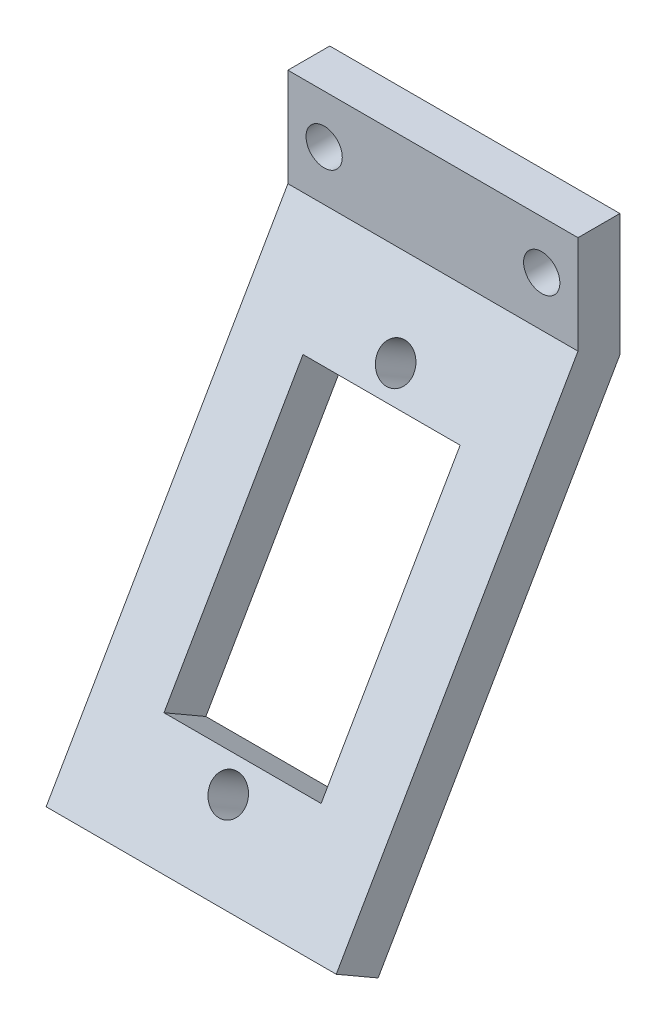
SolidWorks part; units mm, degrees
ref_plane "前视基准面" through (0, 0, 0) normal (0, 0, 1) x (1, 0, 0)
ref_plane "上视基准面" through (0, 0, 0) normal (0, 1, 0) x (1, 0, 0)
ref_plane "右视基准面" through (0, 0, 0) normal (1, 0, 0) x (0, 0, -1)
ref_axis "基准轴1" through (73.7735, 0, 0) along (-1, 0, 0)
ref_plane "基准面2" through (0, 0, 0) normal (0, 0.5, 0.866) x (-1, 0, 0)
ref_axis "基准轴2" through (0, 0, 97.5114) along (0, 0, -1)
ref_plane "基准面3" through (0, 43, 74.4782) normal (0, 0.5, 0.866) x (-1, 0, 0)
sketch "草图4" plane through (0, 43, 74.4782) normal (0, 0.5, 0.866) x (-1, 0, 0)
  line L1 (-6.5, -11.5) -> (6.5, -11.5)
  line L2 (-6.5, -11.5) -> (-6.5, 11.5)
  line L3 (-6.5, 11.5) -> (6.5, 11.5)
  line L4 (6.5, -11.5) -> (6.5, 11.5)
  line L5 (-6.5, -11.5) -> (6.5, 11.5) construction
  line L6 (-6.5, 11.5) -> (6.5, -11.5) construction
  line L7 (-12, -20) -> (12, -20)
  line L8 (-12, -20) -> (-12, 20)
  line L9 (-12, 20) -> (12, 20)
  line L10 (12, -20) -> (12, 20)
  line L11 (-12, -20) -> (12, 20) construction
  line L12 (-12, 20) -> (12, -20) construction
  point P0 (0, 0)
  point P6 (0, 0)
  dimension "D1" = 13
  dimension "D2" = 23
  dimension "D3" = 40
  dimension "D4" = 24
ref_axis "基准轴3" through (0, 77.466, 0) along (0, -1, 0)
ref_plane "基准面4" through (0, 75, 0) normal (0, 1, 0) x (1, 0, 0)
sketch "草图7" plane through (0, 43, 74.4782) normal (0, 0.5, 0.866) x (-1, 0, 0)
  line L0 (0, 48.7557) -> (0, -37.4519) construction
  line L1 (-73.7735, 0) -> (73.7735, 0) construction
  line L2 (0, 0) -> (14.5173, 0) construction
  circle A0 centre (0, 13.85) radius 1.5
  circle A1 centre (0, -13.85) radius 1.5
  point P11 (0, 0)
  dimension "D1" = 13.85
sketch "草图11" plane through (0, 43, 74.4782) normal (0, 0.5, 0.866) x (-1, 0, 0)
  line L0 (-37.6337, -5.25) -> (37.614, -5.25) construction
  line L1 (-73.7735, 0) -> (73.7735, 0) construction
  line L3 (-12.0099, -25.25) -> (11.9901, -25.25)
  line L4 (-12.0099, -25.25) -> (-12.0099, 14.75)
  line L5 (-12.0099, 14.75) -> (11.9901, 14.75)
  line L6 (11.9901, -25.25) -> (11.9901, 14.75)
  line L7 (-12.0099, -25.25) -> (11.9901, 14.75) construction
  line L8 (-12.0099, 14.75) -> (11.9901, -25.25) construction
  line L9 (-6.5099, -16.75) -> (6.4901, -16.75)
  line L10 (-6.5099, -16.75) -> (-6.5099, 6.25)
  line L11 (-6.5099, 6.25) -> (6.4901, 6.25)
  line L12 (6.4901, -16.75) -> (6.4901, 6.25)
  line L13 (-6.5099, -16.75) -> (6.4901, 6.25) construction
  line L14 (-6.5099, 6.25) -> (6.4901, -16.75) construction
  point P4 (-0.0099, -5.25)
  point P9 (-0.0099, -5.25)
  dimension "D1" = 5.25
  dimension "D2" = 24
  dimension "D3" = 40
  dimension "D4" = 13
  dimension "D5" = 23
extrude "凸台-拉伸1" add sketch "草图11" along normal blind 4
sketch "草图12" plane through (0, 43, 74.4782) normal (0, -0.5, -0.866) x (-1, 0, 0)
  line L0 (0, -48.7557) -> (0, 37.4519) construction
  line L1 (0, 5.25) -> (30.3633, 5.25) construction
  line L2 (6.4901, -6.25) -> (-6.5099, -6.25) construction
  circle A0 centre (0, 19.1) radius 1.5
  circle A1 centre (0, -8.6) radius 1.5
  dimension "D1" = 27.7
  dimension "D3" = 13.85
  dimension "D4" = 11.5
extrude "切除-拉伸1" cut sketch "草图12" against normal blind 4 contours A0 | A1
sketch "草图13" plane through (0, 75, 0) normal (0, 1, 0) x (1, 0, 0)
  line L4 (12.0099, -61.8532) -> (-11.9901, -61.8532)
  line L5 (-11.9901, -61.8532) -> (-11.9901, -65.3173)
  line L6 (-11.9901, -65.3173) -> (12.0099, -65.3173)
  line L7 (12.0099, -65.3173) -> (12.0099, -61.8532)
  line L8 (12.0099, -61.8532) -> (-11.9901, -61.8532)
  line L9 (-11.9901, -61.8532) -> (-11.9901, -65.3173)
  line L10 (-11.9901, -65.3173) -> (12.0099, -65.3173)
  line L11 (12.0099, -65.3173) -> (12.0099, -61.8532)
  dimension "D1" = 0
extrude "凸台-拉伸2" add sketch "草图13" against normal up to surface (8.1329 mm away) up to face at (0.0099, 65.8671, 63.5852)
sketch "草图14" plane through (0, 0, 61.8532) normal (0, 0, -1) x (-1, 0, 0)
  line L2 (12.9053, 75) -> (-12.9053, 75) construction
  line L3 (11.9901, 64.8671) -> (11.9901, 75) construction
  line L4 (-12.0099, 64.8671) -> (-12.0099, 75) construction
  circle A0 centre (8.9901, 71) radius 1.5
  circle A1 centre (-9.0099, 71) radius 1.5
  dimension "D1" = 3
  dimension "D2" = 3
  dimension "D3" = 4
  dimension "D4" = 3
  dimension "D5" = 4
  dimension "D6" = 3
extrude "切除-拉伸2" cut sketch "草图14" against normal blind 4
